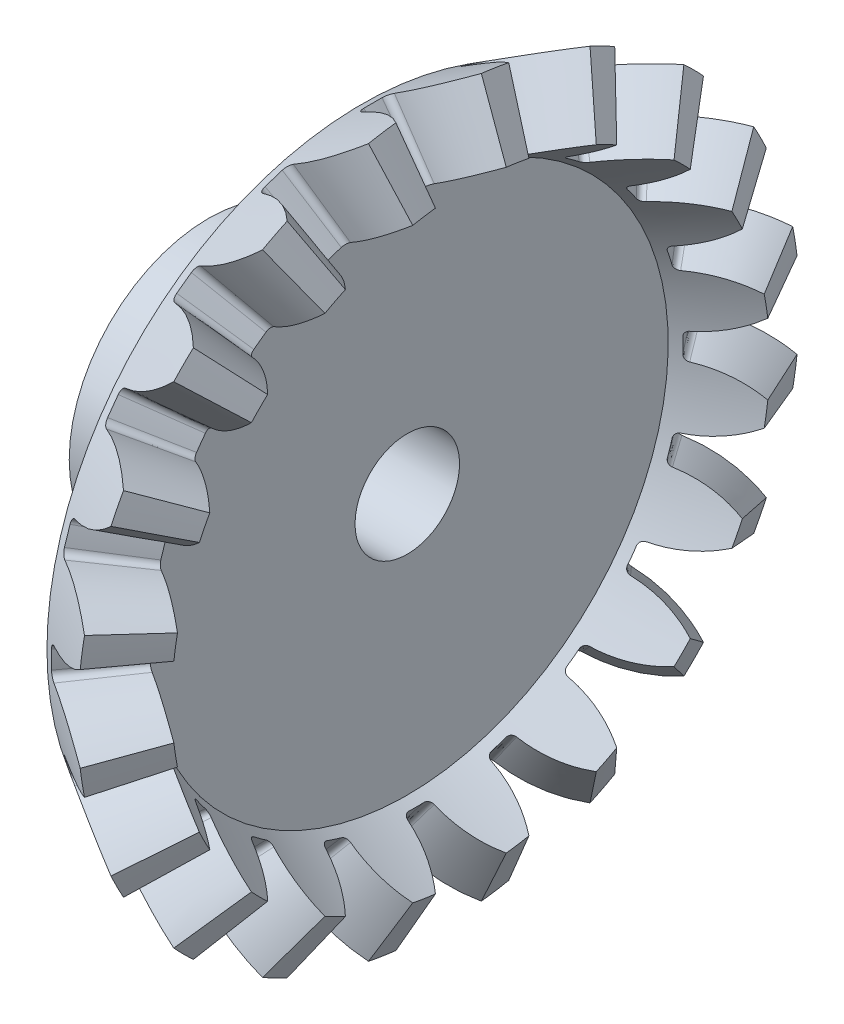
SolidWorks part; units mm, degrees
revolve "Base-Revolve" add sketch "BasProSke" angle 360 about L0 other way angle 9
sketch "BasProSke" plane through (0, 0, 0) normal (0, 1, 0) x (1, 0, 0)
  line L0 (-10, 0) -> (60, 0) construction
  line L1 (0, 0) -> (0, 57.4135)
  line L2 (0, 0) -> (8.2738, 0)
  line L3 (8.2738, 0) -> (8.2738, 47.5672)
  line L4 (48.2442, 0) -> (-6.1702, 90.6907) construction
  line L5 (0, 57.4135) -> (13.9862, 65.8052)
  line L6 (48.2442, 0) -> (-11.1603, 114.1085) construction
  line L7 (48.2442, 0) -> (0, 57.4135) construction
  line L8 (13.9862, 65.8052) -> (19.8614, 54.5197)
  line L9 (19.8614, 54.5197) -> (8.2738, 47.5672)
  line L10 (10.1442, 63.5) -> (-1.8402, 63.5) construction
  dimension "D1" = 114.827
  dimension "D2" = 48.2442
  dimension "D3" = 74.0531
  dimension "D4" = 3.462
ref_plane "Plane1" through (0, 0, 0) normal (0, 0, 1) x (1, 0, 0)
ref_plane "Plane2" through (0, 0, 0) normal (0, 1, 0) x (1, 0, 0)
ref_plane "Plane3" through (0, 0, 0) normal (1, 0, 0) x (0, 0, -1)
sketch "HoldingSke" plane through (0, 0, 0) normal (0, 1, 0) x (1, 0, 0)
  line L0 (0, 0) -> (92.8162, -41.3244)
  line L1 (-15, 0) -> (100, 0) construction
  line L2 (0, 0) -> (-82.0105, 7.681)
  line L3 (0, 0) -> (-11.863, 4.5341)
  line L4 (0, 0) -> (8.1152, 2.9537)
  line L5 (0, 0) -> (-71.3958, -26.6285)
  line L6 (0, 0) -> (-10.5278, -7.1032)
  line L7 (-82.0105, 7.681) -> (-81.4384, 83.8789)
  line L8 (-76.2, 54.61) -> (-54.61, 54.61)
  line L9 (-71.009, 38.7566) -> (-53.1078, 45.2721)
  line L10 (-76.2, 71.12) -> (104.1128, 71.12)
  line L11 (0, 0) -> (-12.7, 0)
  line L12 (-76.2, 101.6) -> (-75.9714, 101.6)
  line L13 (24.9733, 27.94) -> (52.954, 28.2846)
  line L14 (24.9733, 27.94) -> (25.0241, 27.9398)
  line L15 (24.9733, 27.94) -> (100.3933, 29.8918)
  line L16 (-82.0105, 7.681) -> (44.2755, -19.1619)
  circle A0 centre (0, 0) radius 9.525
  circle A1 centre (0, 0) radius 25.4
  circle A2 centre (0, 0) radius 25.4
  circle A3 centre (0, 0) radius 9.525
  dimension "Num_teeth" = 20
  dimension "Pitch_radius" = 180.3128
  dimension "Width" = 12.7
ref_plane "ToothPln" through (6.9931, 61.6094, 0) normal (-0.5145, 0.8575, 0) x (0, 0, -1)
ref_plane "ToothPln2" through (12.7705, -21.2842, 0) normal (-0.5145, 0.8575, 0) x (0, 0, 1)
sketch "TooCutSke" plane through (6.9931, 61.6094, 0) normal (-0.5145, 0.8575, 0) x (0, 0, -1)
  line L2 (0, 59.8253) -> (274.7086, -1674.6166) construction
  line L3 (0, 59.8253) -> (146.9816, -1765.6112) construction
  line L4 (0, -15.621) -> (0, 105.791) construction
  line L6 (-24.765, -8.1553) -> (21.082, -8.1553) construction
  line L7 (9.9336, -2.893) -> (5.0814, -3.2836) construction
  arc A0 (-8.6464, -8.9737) -> (8.6464, -8.9737) centre (0, 59.8253) ccw
  arc A1 (-1.6508, 5.8145) -> (1.6508, 5.8145) centre (0, 59.8253) ccw
  circle A2 centre (0, 59.8253) radius 63.5 construction
  circle A3 centre (0, 59.8253) radius 59.6705 construction
  arc A4 (2.9271, 4.6951) -> (1.6508, 5.8145) centre (1.6888, 4.5705) ccw
  arc A5 (2.9271, 4.6951) -> (8.6464, -8.9737) centre (28.1995, 7.2386) ccw
  arc A6 (-8.6464, -8.9737) -> (-2.9271, 4.6951) centre (-28.1995, 7.2386) ccw
  arc A7 (-1.6508, 5.8145) -> (-2.9271, 4.6951) centre (-1.6888, 4.5705) ccw
  ellipse E0 centre (0, 25.7012) end of major axis (65.8052, 25.7012) minor radius 33.8565 construction
sketch "TooCutSke2" plane through (12.7705, -21.2842, 0) normal (-0.5145, 0.8575, 0) x (0, 0, 1)
  line L0 (0, 0) -> (0, 68.072) construction
  line L2 (21.082, 29.539) -> (-20.32, 29.539) construction
  circle A0 centre (0, 41.369) radius 0.0127
  ellipse E1 centre (0, 0) end of major axis (-57.4135, 0) minor radius 29.539 construction
loft "ToothCut" cut profiles "TooCutSke2", "TooCutSke"
pattern_circular "TeethCuts" count 20 every 18 about axis through (-10, 0, 0) along (1, 0, 0) of "ToothCut"
sketch "HubSke" plane through (0, 0, 0) normal (-1, 0, 0) x (0, 0, 1)
  circle A0 centre (0, 0) radius 25.4
  dimension "Diameter" = 50.8
extrude "Hub" add sketch "HubSke" along normal blind 27.9559
sketch "BorSke" plane through (0, 0, 0) normal (1, 0, 0) x (0, 0, -1)
  circle A0 centre (0, 0) radius 9.525
  dimension "Diameter" = 19.05
extrude "Bore" cut sketch "BorSke" along normal mid plane 152.4001
sketch "KeySke" plane through (0, 0, 0) normal (1, 0, 0) x (0, 0, -1)
  line L0 (-3.175, 0) -> (-3.175, 12.065)
  line L1 (-3.175, 12.065) -> (3.175, 12.065)
  line L2 (3.175, 12.065) -> (3.175, 0)
  line L3 (0, 0) -> (0, 34) construction
  line L4 (-3.175, 0) -> (3.175, 0)
  dimension "Offset" = 12.065
extrude "Keyway" [suppressed] cut sketch "KeySke" along normal mid plane 152.4001
pattern_circular "Keyway2" [suppressed] count 2 every 90 about axis through (-10, 0, 0) along (1, 0, 0)
equation "' \"Pitch@HoldingSke\" = 4"
equation "' \"Num_teeth@HoldingSke\" = 20"
equation "' \"Mating_teeth@HoldingSke\" = 12"
equation "' \"Ap@HoldingSke\" =  20"
equation "' \"Ap@HoldingSke\" = 20"
equation "' \"Width@HoldingSke\" = 0.5"
equation "' \"Hub_dia@HoldingSke\"= 2"
equation "' \"Hub_dia@HoldingSke\" = 2"
equation "' \"Mounting_dist@HoldingSke\" = 3"
equation "' \"Bore@HoldingSke\" = 0.75"
equation "' \"T_dim@HoldingSke\" = 0.85"
equation "' \"Width@KeySke\" = 0.25"
equation "' \"Show_teeth@HoldingSke\" = 100"
equation "' \"Backlash@HoldingSke\" = 0.009"
equation "' \"Addendum_fac@HoldingSke\" = 1.0"
equation "' \"Dedendum_fac@HoldingSke\" = 1.188"
equation "' \"Dedendum_add@HoldingSke\" = 0.002"
equation "' \"Clearance_fac@HoldingSke\" = 0.188"
equation " \"Addendum_fac@HoldingSke\" = 0.54 + 0.46 / (\"Num_teeth@HoldingSke\" /  \"Mating_teeth@HoldingSke\" ) ^ 2"
equation "' \"Addendum_fac@HoldingSke\" = 2 - (0.54 + 0.46 / (\"Mating_teeth@HoldingSke\" /  \"Num_teeth@HoldingSke\" ) ^ 2)"
equation "\"Dedendum_fac@HoldingSke\" = 2.188 - \"Addendum_fac@HoldingSke\""
equation "\"Pitch_rad@BasProSke\" = \"Num_teeth@HoldingSke\" / \"Pitch@HoldingSke\" / 2"
equation "\"Pitch_ang@BasProSke\" = atn(\"Num_teeth@HoldingSke\" / \"Mating_teeth@HoldingSke\") * (180 / 3.14159265)"
equation "\"Addendum@BasProSke\" = \"Addendum_fac@HoldingSke\" / \"Pitch@HoldingSke\""
equation "\"Dedendum_plus@BasProSke\" = (\"Dedendum_fac@HoldingSke\" / \"Pitch@HoldingSke\" + \"Dedendum_add@HoldingSke\") * 1.25"
equation "\"Face_wid@BasProSke\" = \"Width@HoldingSke\""
equation "\"Radius@TooCutSke\" = ((\"Num_teeth@HoldingSke\" + 2 * \"Addendum_fac@HoldingSke\") / \"Pitch@HoldingSke\" ) / 2"
equation "\"Overcut_dia@TooCutSke\" =  1.02 * (\"Num_teeth@HoldingSke\" + 2 * \"Addendum_fac@HoldingSke\") / \"Pitch@HoldingSke\""
equation "\"Pitch_dia@TooCutSke\" = \"Num_teeth@HoldingSke\" / \"Pitch@HoldingSke\""
equation "\"Base_dia@TooCutSke\" = \"Num_teeth@HoldingSke\" / \"Pitch@HoldingSke\" * cos((\"Ap@HoldingSke\"  * 3.14159265 / 180))"
equation "'  \"Root_dia@TooCutSke\" =  (\"Num_teeth@HoldingSke\" + 2) / \"Pitch@HoldingSke\" - 2 * (\"Addendum_fac@HoldingSke\" + \"Dedendum_fac@HoldingSke\") / \"Pitch@HoldingSke\" - \"Dedendum_add@HoldingSke\" * 2"
equation "'  \"Root_dia@TooCutSke\" = (\"Num_teeth@HoldingSke\" + 2) / \"Pitch@HoldingSke\" - 2 * (\"Addendum_fac@HoldingSke\" + \"Dedendum_fac@HoldingSke\") / \"Pitch@HoldingSke\" - \"Dedendum_add@HoldingSke\" * 2"
equation "\"Root_dia@TooCutSke\" =  \"Num_teeth@HoldingSke\" / \"Pitch@HoldingSke\" - 2 * \"Dedendum_fac@HoldingSke\" / \"Pitch@HoldingSke\" - \"Dedendum_add@HoldingSke\" * 2"
equation "\"Half_ang@TooCutSke\" = 180 / \"Num_teeth@HoldingSke\""
equation "\"Half_CT@TooCutSke\" = \"Num_teeth@HoldingSke\" / \"Pitch@HoldingSke\" * sin((3.14159265 / 2 / \"Num_teeth@HoldingSke\")) / 2 - 2 * \"Backlash@HoldingSke\" / 4"
equation "\"Flank_rad@TooCutSke\" = \"Num_teeth@HoldingSke\" / \"Pitch@HoldingSke\" / 5"
equation "\"Root_fillet@TooCutSke\" = \"Clearance_fac@HoldingSke\" / \"Pitch@HoldingSke\" + \"Dedendum_add@HoldingSke\""
equation "\"Offset@ToothPln2\"  = \"Num_teeth@HoldingSke\" / \"Pitch@HoldingSke\" / 2 / sin(atn(\"Num_teeth@HoldingSke\" / \"Mating_teeth@HoldingSke\"))"
equation "\"Dedendum_plus@TooCutSke2\" = \"Dedendum_plus@BasProSke\""
equation "\"MHD@HoldingSke\" = \"Num_teeth@HoldingSke\" / \"Pitch@HoldingSke\" - 2 * \"Dedendum_plus@BasProSke\" * cos(atn(\"Num_teeth@HoldingSke\" / \"Mating_teeth@HoldingSke\"))"
equation "\"MBD@HoldingSke\" = \"Num_teeth@HoldingSke\" / \"Pitch@HoldingSke\" - 2 * \"Dedendum_plus@BasProSke\" * cos(atn(\"Num_teeth@HoldingSke\" / \"Mating_teeth@HoldingSke\")) - 0.002"
equation "\"MnMD@HoldingSke\" =  \"Num_teeth@HoldingSke\" / \"Pitch@HoldingSke\" / 2 / (\"Num_teeth@HoldingSke\" / \"Mating_teeth@HoldingSke\") + \"Dedendum_plus@BasProSke\" * sin(atn(\"Num_teeth@HoldingSke\" / \"Mating_teeth@HoldingSke\"))"
equation "\"OAL@HoldingSke\" = \"MnMD@HoldingSke\""
equation "\"MHD@HoldingSke\" = ((sgn( \"MHD@HoldingSke\" - \"Hub_dia@HoldingSke\" )-1)*( \"MHD@HoldingSke\" - \"Hub_dia@HoldingSke\" ))/-2+ \"Hub_dia@HoldingSke\""
equation "\"MBD@HoldingSke\" = ((sgn( \"MBD@HoldingSke\" - \"Bore@HoldingSke\" )-1)*( \"MBD@HoldingSke\" - \"Bore@HoldingSke\" ))/-2+ \"Bore@HoldingSke\""
equation "\"Face_wid@BasProSke\" = ((sgn( \"Face_wid@BasProSke\" - \"Offset@ToothPln2\" * 0.9)-1)*( \"Face_wid@BasProSke\" - \"Offset@ToothPln2\" * 0.9))/-2+ \"Offset@ToothPln2\" * 0.9"
equation "\"OAL@HoldingSke\" = ((sgn( \"OAL@HoldingSke\" - \"Mounting_dist@HoldingSke\" )+1)*( \"OAL@HoldingSke\" - \"Mounting_dist@HoldingSke\" ))/2 + \"Mounting_dist@HoldingSke\" + 0.000002"
equation "\"Num_teeth@TeethCuts\" = int( \"Show_teeth@HoldingSke\" ) + 1"
equation "\"Num_teeth@TeethCuts\" = ((sgn( \"Num_teeth@TeethCuts\" - \"Num_teeth@HoldingSke\" )-1)*( \"Num_teeth@TeethCuts\" - \"Num_teeth@HoldingSke\" ))/-2+ \"Num_teeth@HoldingSke\""
equation "\"Num_teeth@TeethCuts\" = ((sgn( \"Num_teeth@TeethCuts\" - 2.0)+1)*( \"Num_teeth@TeethCuts\" - 2.0))/2 +2.0"
equation "\"Angle@TeethCuts\" = 360.0 / \"Num_teeth@HoldingSke\""
equation "\"Diameter@HubSke\" = \"MHD@HoldingSke\""
equation "\"Length@Hub\" = \"OAL@HoldingSke\" - \"MnMD@HoldingSke\" + 0.000002"
equation "\"Diameter@BorSke\" = \"MBD@HoldingSke\""
equation "\"D1@Bore\" = \"OAL@HoldingSke\" * 2.0"
equation "\"D1@Keyway\" = \"OAL@HoldingSke\" * 2.0"
equation "\"Offset@KeySke\" = \"T_dim@HoldingSke\" - \"MBD@HoldingSke\" / 2.0"
